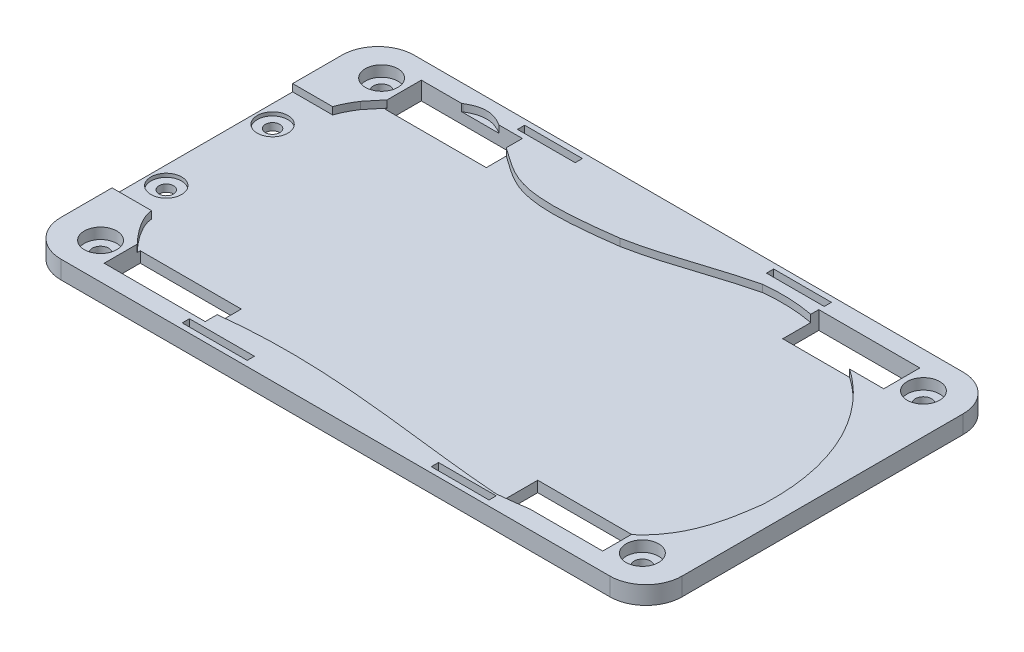
SolidWorks part; units mm, degrees
ref_plane "Front Plane" through (0, 0, 0) normal (0, 0, 1) x (1, 0, 0)
ref_plane "Top Plane" through (0, 0, 0) normal (0, 1, 0) x (1, 0, 0)
ref_plane "Right Plane" through (0, 0, 0) normal (1, 0, 0) x (0, 0, -1)
sketch "Sketch1" plane through (0, 0, 0) normal (0, 1, 0) x (1, 0, 0)
  line L1 (-78.1571, 35.933) -> (-78.1571, -14.1122)
  line L2 (78.9797, 0.0343) -> (-78.1571, 0.0343) construction
  line L3 (-77.1571, 35.7646) -> (-77.1571, -14.1122)
  line L4 (78.9797, -0.9657) -> (-78.1571, -0.9657)
  arc A1 (37.8695, -35.2975) -> (39.5975, -35.2134) centre (38.2635, -25.6055) ccw
  arc A2 (37.9263, -34.299) -> (39.4753, -34.2207) centre (38.2635, -25.6055) ccw
  spline S0 degree 1 poles (-77.1571, -14.1122) (-56.919, -31.9168) knots 0 0 1 1 construction
  spline S1 degree 1 poles (-56.919, -31.9168) (37.9263, -34.299) knots 0 0 1 1 construction
  spline S2 degree 1 poles (39.4753, -34.2207) (77.9849, 0.1477) knots 0 0 1 1 construction
  spline S3 degree 1 poles (77.9849, 0.1477) (25.0602, 52.8732) knots 0 0 1 1 construction
  spline S4 degree 1 poles (25.0602, 52.8732) (-5.6593, 44.1904) knots 0 0 1 1 construction
  spline S5 degree 1 poles (-5.6593, 44.1904) (-43.9853, 50.6886) knots 0 0 1 1 construction
  spline S6 degree 1 poles (-43.9853, 50.6886) (-59.7702, 54.7238) knots 0 0 1 1 construction
  spline S7 degree 1 poles (-59.7702, 54.7238) (-74.5158, 41.0521) knots 0 0 1 1 construction
  spline S8 degree 1 poles (-74.5158, 41.0521) (-77.1571, 35.7646) knots 0 0 1 1 construction
  spline S9 degree 3 poles (-77.1571, -14.1122) (-77.1565, -14.3701) (-77.1092, -14.8732) (-76.8359, -15.9559) (-76.1879, -17.5008) (-75.044, -19.4183) (-73.152, -22.0092) (-70.3495, -25.0822) (-66.8736, -28.0972) (-63.6864, -30.2141) (-61.0019, -31.4062) (-58.8274, -31.848) (-57.5718, -31.8794) (-56.919, -31.9168) knots 0.000484 0.000484 0.000484 0.000484 0.031521 0.062558 0.124632 0.186706 0.248781 0.372929 0.497077 0.621225 0.745373 0.869521 0.993669 0.993669 0.993669 0.993669
  spline S10 degree 3 poles (-56.919, -31.9168) (-56.6769, -31.8873) (-56.2021, -31.8274) (-55.1791, -31.687) (-53.8294, -31.4877) (-52.0759, -31.2184) (-49.5744, -30.8354) (-46.1465, -30.3372) (-41.5825, -29.7813) (-36.5976, -29.3261) (-29.4274, -28.913) (-19.5571, -28.8468) (-6.4839, -29.5875) (5.2448, -30.7865) (15.023, -31.9295) (22.521, -32.809) (30.1538, -33.642) (35.3408, -34.1075) (37.9263, -34.299) knots 0.000538 0.000538 0.000538 0.000538 0.016152 0.031766 0.062993 0.094221 0.125449 0.187904 0.250359 0.312815 0.37527 0.50018 0.625091 0.750001 0.812457 0.874912 0.937367 0.999822 0.999822 0.999822 0.999822
  spline S11 degree 3 poles (39.4753, -34.2207) (41.0079, -34.0574) (44.09, -33.7147) (50.0835, -32.8429) (57.0969, -31.1859) (64.2184, -27.8839) (69.7763, -23.1857) (73.0497, -18.2789) (74.9177, -14.0269) (75.9805, -10.7732) (76.7509, -7.5724) (77.1995, -5.064) (77.4798, -3.2279) (77.6607, -1.9649) (77.8261, -0.8108) (77.9301, -0.1834) (77.9849, 0.1477) knots -0.000309 -0.000309 -0.000309 -0.000309 0.063093 0.126495 0.253299 0.380104 0.506908 0.633712 0.697114 0.760516 0.823918 0.88732 0.919021 0.950722 0.982423 1.014124 1.014124 1.014124 1.014124
  spline S12 degree 3 poles (77.9849, 0.1477) (78.0286, 1.2633) (78.0637, 3.5224) (77.9426, 6.757) (77.6596, 9.9047) (77.0733, 13.9671) (75.9626, 18.7836) (73.4433, 25.9357) (69.0206, 33.8098) (62.0495, 41.4932) (53.7895, 47.3444) (44.6121, 51.2947) (34.9036, 53.2804) (28.3113, 53.2357) (25.0602, 52.8732) knots 0.000169 0.000169 0.000169 0.000169 0.031414 0.062658 0.093902 0.125147 0.187635 0.250124 0.375101 0.500079 0.625056 0.750034 0.875011 0.999988 0.999988 0.999988 0.999988
  spline S13 degree 3 poles (25.0602, 52.8732) (19.8954, 51.6294) (12.3224, 49.1317) (2.1607, 45.9713) (-3.0371, 44.6913) (-5.6593, 44.1904) knots 0.000659 0.000659 0.000659 0.000659 0.498067 0.746772 0.995476 0.995476 0.995476 0.995476
  spline S14 degree 3 poles (-5.6593, 44.1904) (-6.6879, 44.0461) (-8.7287, 43.7719) (-12.9633, 43.2668) (-18.1826, 42.7952) (-23.9015, 42.6322) (-28.8306, 42.9899) (-32.9666, 43.9514) (-35.9177, 45.2914) (-38.1959, 46.6779) (-39.9392, 47.8658) (-41.507, 48.9798) (-42.8638, 49.9292) (-43.6163, 50.4405) (-43.9853, 50.6886) knots -0.000196 -0.000196 -0.000196 -0.000196 0.062587 0.12537 0.250936 0.376501 0.502067 0.627632 0.753198 0.815981 0.878764 0.941546 0.972938 1.004329 1.004329 1.004329 1.004329
  spline S15 degree 3 poles (-43.9853, 50.6886) (-44.2445, 50.8673) (-44.7682, 51.2325) (-45.7507, 51.9331) (-46.8912, 52.7591) (-48.146, 53.6496) (-49.6971, 54.6811) (-51.4608, 55.6487) (-53.4077, 56.2593) (-55.2517, 56.3574) (-56.711, 56.0808) (-57.7948, 55.7138) (-58.5465, 55.3915) (-59.2299, 55.0428) (-59.5837, 54.8359) (-59.7702, 54.7238) knots -0.002497 -0.002497 -0.002497 -0.002497 0.029066 0.060629 0.123754 0.18688 0.250006 0.376257 0.502509 0.62876 0.755012 0.818137 0.881263 0.944389 1.007515 1.007515 1.007515 1.007515
  spline S16 degree 3 poles (-78.1571, -14.1122) (-78.1559, -14.7524) (-77.9173, -15.9777) (-77.0678, -17.9828) (-75.8538, -20.0098) (-73.8827, -22.6985) (-70.9901, -25.8584) (-67.4096, -28.9504) (-64.0991, -31.1349) (-61.2379, -32.3904) (-59.243, -32.7789) (-57.8421, -32.8756) (-57.2118, -32.9007) (-56.8882, -32.9203) knots 0.000409 0.000409 0.000409 0.000409 0.062843 0.125276 0.18771 0.250143 0.375011 0.499878 0.624745 0.749612 0.874479 0.936913 0.999346 0.999346 0.999346 0.999346
  spline S17 degree 3 poles (-56.8882, -32.9203) (-56.6427, -32.8908) (-56.1603, -32.8306) (-55.1309, -32.6904) (-53.7754, -32.491) (-52.0233, -32.2221) (-49.5292, -31.8398) (-46.1189, -31.3427) (-41.5829, -30.7872) (-36.6286, -30.3313) (-29.4997, -29.9158) (-19.6749, -29.8441) (-6.6369, -30.5782) (5.0856, -31.7749) (14.8757, -32.919) (22.3927, -33.8009) (30.0532, -34.6371) (35.2704, -35.1052) (37.8695, -35.2975) knots -0.001373 -0.001373 -0.001373 -0.001373 0.014273 0.029919 0.06121 0.092502 0.123794 0.186377 0.24896 0.311543 0.374127 0.499293 0.62446 0.749626 0.81221 0.874793 0.937376 0.99996 0.99996 0.99996 0.99996
  spline S18 degree 3 poles (39.5975, -35.2134) (41.1398, -35.049) (44.2356, -34.7045) (50.3018, -33.8209) (57.4502, -32.1301) (64.7991, -28.7164) (70.5782, -23.8111) (73.9656, -18.7006) (75.8832, -14.3057) (76.9672, -10.962) (77.7479, -7.6914) (78.1997, -5.145) (78.4804, -3.2966) (78.6613, -2.0308) (78.824, -0.9009) (78.9276, -0.2806) (78.9816, 0.0458) knots -0.000086 -0.000086 -0.000086 -0.000086 0.063428 0.126941 0.253967 0.380993 0.50802 0.635046 0.698559 0.762072 0.825585 0.889098 0.920855 0.952612 0.984368 1.016125 1.016125 1.016125 1.016125
  spline S19 degree 3 poles (78.9816, 0.0458) (79.0271, 1.1797) (79.0647, 3.4739) (78.9444, 6.7697) (78.6587, 9.9749) (78.0642, 14.1169) (76.9341, 19.0326) (74.3646, 26.3398) (69.8439, 34.3944) (62.712, 42.2543) (54.2626, 48.2351) (44.8799, 52.2671) (34.9529, 54.2886) (28.2109, 54.2351) (24.8869, 53.8601) knots -0.000407 -0.000407 -0.000407 -0.000407 0.03088 0.062166 0.093453 0.12474 0.187314 0.249888 0.375035 0.500183 0.62533 0.750478 0.875625 1.000773 1.000773 1.000773 1.000773
  spline S20 degree 3 poles (24.8869, 53.8601) (22.2839, 53.2349) (17.1223, 51.77) (6.9788, 48.4835) (-0.6206, 46.1711) (-5.8226, 45.1772) knots -0.001281 -0.001281 -0.001281 -0.001281 0.247714 0.49671 0.9947 0.9947 0.9947 0.9947
  spline S21 degree 3 poles (-5.8226, 45.1772) (-6.8463, 45.0337) (-8.8779, 44.761) (-13.0882, 44.2593) (-18.2643, 43.7927) (-23.9018, 43.6338) (-28.7026, 43.9859) (-32.6523, 44.9085) (-35.4477, 46.177) (-37.6484, 47.5152) (-39.3619, 48.6824) (-40.9248, 49.793) (-42.292, 50.7496) (-43.0505, 51.2651) (-43.4225, 51.5151) knots 0.000305 0.000305 0.000305 0.000305 0.063048 0.125791 0.251276 0.376761 0.502247 0.627732 0.753218 0.815961 0.878703 0.941446 0.972817 1.004189 1.004189 1.004189 1.004189
  spline S22 degree 3 poles (-43.4225, 51.5151) (-43.6786, 51.6918) (-44.1958, 52.0526) (-45.1684, 52.7462) (-46.308, 53.5714) (-47.577, 54.4721) (-49.1727, 55.5335) (-51.0441, 56.5648) (-53.2147, 57.2519) (-55.3195, 57.3652) (-56.9568, 57.0533) (-58.1477, 56.6506) (-58.9689, 56.2985) (-59.5708, 55.992) (-60.0059, 55.7483) (-60.1862, 55.6406) (-60.2803, 55.5839) knots -0.002294 -0.002294 -0.002294 -0.002294 0.029245 0.060783 0.12386 0.186936 0.250013 0.376167 0.50232 0.628473 0.754627 0.817704 0.88078 0.943857 0.975396 1.006934 1.006934 1.006934 1.006934
  spline S23 degree 3 poles (-60.2803, 55.5839) (-60.715, 55.3297) (-61.582, 54.801) (-63.2222, 53.7187) (-65.9105, 51.7373) (-69.2431, 48.741) (-72.0244, 45.6929) (-73.7392, 43.6279) (-74.6657, 42.4756) (-75.1049, 41.9202) (-75.3265, 41.639) knots 0.000427 0.000427 0.000427 0.000427 0.063268 0.126109 0.251792 0.503158 0.754524 0.880206 0.943048 1.005889 1.005889 1.005889 1.005889
  spline S24 degree 3 poles (-59.7702, 54.7238) (-60.1936, 54.4761) (-61.0386, 53.9612) (-62.6368, 52.9072) (-65.2587, 50.9763) (-68.5171, 48.0498) (-71.2443, 45.0657) (-73.1899, 42.7247) (-74.0698, 41.6179) (-74.5158, 41.0521) knots 0.000174 0.000174 0.000174 0.000174 0.062881 0.125589 0.251004 0.501833 0.752662 0.878077 1.003492 1.003492 1.003492 1.003492
  spline S25 degree 3 poles (-74.5158, 41.0521) (-75.0658, 40.2217) (-76.0765, 38.4779) (-76.8336, 36.6875) (-77.1571, 35.7646) knots 0.499549 0.499549 0.499549 0.499549 0.499766 0.499983 0.499983 0.499983 0.499983
  spline S26 degree 3 poles (-75.3265, 41.639) (-75.92, 40.746) (-77.0064, 38.8701) (-77.815, 36.9314) (-78.1571, 35.933) knots 0.499546 0.499546 0.499546 0.499546 0.49977 0.499995 0.499995 0.499995 0.499995
  point P0 (0.4631, 0.0343)
  dimension "D1" = 1
sketch "Sketch6" plane through (0, 0, 0) normal (0, 1, 0) x (1, 0, 0)
  line L0 (-78.1571, 35.933) -> (-78.1571, -14.1122) construction
  line L1 (73.9816, 59.5839) -> (-78.1571, 59.5839)
  line L2 (83.9816, 49.5839) -> (83.9816, -28.2975)
  line L3 (73.9816, -38.2975) -> (-78.1571, -38.2975)
  line L4 (-88.1571, 49.5839) -> (-88.1571, -28.2975)
  arc A0 (-78.1571, -38.2975) -> (-88.1571, -28.2975) centre (-78.1571, -28.2975) cw
  arc A1 (-88.1571, 49.5839) -> (-78.1571, 59.5839) centre (-78.1571, 49.5839) cw
  arc A2 (73.9816, 59.5839) -> (83.9816, 49.5839) centre (73.9816, 49.5839) cw
  arc A3 (83.9816, -28.2975) -> (73.9816, -38.2975) centre (73.9816, -28.2975) cw
  dimension "D5" = 10
  dimension "D1" = 5
  dimension "D2" = 10
  dimension "D3" = 3
  dimension "D4" = 4
extrude "Boss-Extrude2" add sketch "Sketch6" along normal blind 6.5
extrude "Cut-Extrude1" cut sketch "Sketch1" along normal blind 2.5 contours A2 S11 L4 L3 S9 S10 | S24 S25 L3 L4 S11 S12 S13 S14 S15 region at (0.1139, 0, 15.5782) region at (-2.2602, 0, -23.2786)
sketch "Sketch7" plane through (0, 0, 0) normal (0, -1, 0) x (1, 0, 0)
  line L1 (-76.2189, 14.1122) -> (-91.3452, 14.1122)
  line L2 (-76.2189, 14.1122) -> (-76.2189, -35.933)
  line L3 (-76.2189, -35.933) -> (-91.3452, -35.933)
  line L4 (-91.3452, 14.1122) -> (-91.3452, -35.933)
extrude "Cut-Extrude2" cut sketch "Sketch7" against normal up to surface (2.5 mm away) contours L2 L1 L4 L3 up to face at (-19.4492, 2.5, -12.7234)
sketch "Sketch8" plane through (0, 6.5, 0) normal (0, 1, 0) x (1, 0, 0)
  line L0 (83.9816, 10.6432) -> (-88.1571, 10.6432) construction
  line L1 (83.9816, -28.2975) -> (83.9816, 49.5839) construction
  line L2 (-88.1571, 49.5839) -> (-88.1571, -28.2975) construction
  line L3 (-2.0877, 59.5839) -> (-2.0877, -38.2975) construction
  line L4 (73.9816, 59.5839) -> (-78.1571, 59.5839) construction
  line L5 (-78.1571, -38.2975) -> (73.9816, -38.2975) construction
  line L7 (78.9816, 54.5839) -> (38.9816, 54.5839)
  line L8 (78.9816, 54.5839) -> (78.9816, 44.5839)
  line L9 (78.9816, 44.5839) -> (38.9816, 44.5839)
  line L10 (38.9816, 54.5839) -> (38.9816, 44.5839)
  line L22 (38.9816, 49.5839) -> (78.9816, 49.5839) construction
  line L23 (66.9816, 54.5839) -> (66.9816, 44.5839)
  circle A1 centre (72.9816, 49.5839) radius 3.5
  dimension "D6" = 7
  dimension "D1" = 10
  dimension "D2" = 40
  dimension "D3" = 5
  dimension "D4" = 5
  dimension "D5" = 6
  dimension "D7" = 6
sketch "Sketch9" plane through (0, 0, 0) normal (0, -1, 0) x (1, 0, 0)
  circle A0 centre (72.9816, -49.5839) radius 4.5
  dimension "D1" = 9
extrude "Cut-Extrude5" cut sketch "Sketch9" against normal blind 3.5
sketch "Sketch10" plane through (0, 3.5, 0) normal (0, -1, 0) x (1, 0, 0)
  circle A0 centre (72.9816, -49.5839) radius 2.25
  dimension "D1" = 4.5
extrude "Cut-Extrude6" cut sketch "Sketch10" against normal blind 21
extrude "Cut-Extrude8" cut sketch "Sketch8" against normal blind 42 contours L23 L7 L10 L9 region at (52.9816, 6.5, -49.5839)
extrude "Cut-Extrude9" cut sketch "Sketch8<3>" against normal blind 1 contours L7 L23 L9 L8 A1 region at (78.8254, 6.5, -49.5839)
sketch "Sketch8<3>" plane through (0, 6.5, 0) normal (0, 1, 0) x (1, 0, 0) same geometry as "Sketch8"
sketch "Sketch12" plane through (0, 6.5, 0) normal (0, 1, 0) x (1, 0, 0)
  line L0 (-88.1571, 10.6432) -> (83.9816, 10.6432) construction
  line L1 (-88.1571, 49.5839) -> (-88.1571, -28.2975) construction
  line L2 (83.9816, -28.2975) -> (83.9816, 49.5839) construction
  line L3 (-2.0877, 59.5839) -> (-2.0877, -36.8461) construction
  line L4 (73.9816, 59.5839) -> (-78.1571, 59.5839) construction
ref_plane "Plane1" through (0, 0, -10.6432) normal (0, 0, 1) x (1, 0, 0)
ref_plane "Plane2" through (-2.0877, 0, 0) normal (-1, 0, 0) x (0, 0, 1)
mirror "Mirror1" about plane through (0, 0, -10.6432) normal (0, 0, 1) of "Cut-Extrude5", "Cut-Extrude6", "Cut-Extrude8", "Cut-Extrude9"
mirror "Mirror2" about plane through (-2.0877, 0, 0) normal (-1, 0, 0) of "Mirror1", "Cut-Extrude9", "Cut-Extrude8", "Cut-Extrude6", "Cut-Extrude5"
sketch "Sketch13" plane through (0, 6.5, 0) normal (0, 1, 0) x (1, 0, 0)
  line L0 (-83.1571, 44.5839) -> (-43.1571, 44.5839) construction
  line L1 (58.9816, 39.5839) -> (-63.1571, 39.5839)
  line L2 (58.9816, 39.5839) -> (58.9816, -18.2975)
  line L3 (58.9816, -18.2975) -> (-63.1571, -18.2975)
  line L4 (-63.1571, 39.5839) -> (-63.1571, -18.2975)
  line L5 (58.9816, 39.5839) -> (-63.1571, -18.2975) construction
  line L6 (58.9816, -18.2975) -> (-63.1571, 39.5839) construction
  line L7 (-83.1571, -23.2975) -> (-43.1571, -23.2975) construction
  line L8 (83.9816, -28.2975) -> (83.9816, 49.5839) construction
  line L9 (-88.1571, 49.5839) -> (-88.1571, -28.2975) construction
  point P0 (-2.0877, 10.6432)
  dimension "D1" = 5
  dimension "D2" = 5
  dimension "D3" = 25
  dimension "D4" = 25
extrude "Cut-Extrude10" cut sketch "Sketch13" against normal blind 1
sketch "Sketch14" plane through (0, 5.5, 0) normal (0, 1, 0) x (1, 0, 0)
  line L0 (-63.1571, 10.6432) -> (58.9816, 10.6432) construction
  line L1 (-63.1571, 39.5839) -> (-63.1571, -18.2975) construction
  line L2 (58.9816, -18.2975) -> (58.9816, 39.5839) construction
  line L3 (-63.1571, -9.3568) -> (58.9816, -9.3568) construction
  line L4 (-63.1571, 10.6432) -> (58.9816, 10.6432) construction
  line L5 (-63.1571, 30.6432) -> (58.9816, 30.6432) construction
  circle A1 centre (-12.0877, 10.6432) radius 2.5
  circle A2 centre (-32.0877, 10.6432) radius 2.5
  circle A3 centre (-52.0877, 10.6432) radius 2.5
  circle A4 centre (-12.0877, 10.6432) radius 2.5
  circle A5 centre (-32.0877, 10.6432) radius 2.5
  circle A6 centre (7.9123, 10.6432) radius 2.5
  circle A7 centre (-12.0877, 10.6432) radius 2.5
  circle A8 centre (27.9123, 10.6432) radius 2.5
  circle A9 centre (7.9123, 10.6432) radius 2.5
  circle A10 centre (7.9123, 10.6432) radius 2.5
  circle A11 centre (27.9123, 10.6432) radius 2.5
  circle A12 centre (47.9123, 10.6432) radius 2.5
  circle A13 centre (-12.0877, -9.3568) radius 2.5
  circle A14 centre (-32.0877, -9.3568) radius 2.5
  circle A15 centre (-52.0877, -9.3568) radius 2.5
  circle A16 centre (-12.0877, -9.3568) radius 2.5
  circle A17 centre (-32.0877, -9.3568) radius 2.5
  circle A18 centre (7.9123, -9.3568) radius 2.5
  circle A19 centre (-12.0877, -9.3568) radius 2.5
  circle A20 centre (27.9123, -9.3568) radius 2.5
  circle A21 centre (7.9123, -9.3568) radius 2.5
  circle A22 centre (7.9123, -9.3568) radius 2.5
  circle A23 centre (27.9123, -9.3568) radius 2.5
  circle A24 centre (47.9123, -9.3568) radius 2.5
  circle A25 centre (-12.0877, 10.6432) radius 2.5
  circle A26 centre (-32.0877, 10.6432) radius 2.5
  circle A27 centre (-52.0877, 10.6432) radius 2.5
  circle A28 centre (-12.0877, 10.6432) radius 2.5
  circle A29 centre (-32.0877, 10.6432) radius 2.5
  circle A30 centre (7.9123, 10.6432) radius 2.5
  circle A31 centre (-12.0877, 10.6432) radius 2.5
  circle A32 centre (27.9123, 10.6432) radius 2.5
  circle A33 centre (7.9123, 10.6432) radius 2.5
  circle A34 centre (7.9123, 10.6432) radius 2.5
  circle A35 centre (27.9123, 10.6432) radius 2.5
  circle A36 centre (47.9123, 10.6432) radius 2.5
  circle A37 centre (-12.0877, 30.6432) radius 2.5
  circle A38 centre (-32.0877, 30.6432) radius 2.5
  circle A39 centre (-52.0877, 30.6432) radius 2.5
  circle A40 centre (-12.0877, 30.6432) radius 2.5
  circle A41 centre (-32.0877, 30.6432) radius 2.5
  circle A42 centre (7.9123, 30.6432) radius 2.5
  circle A43 centre (-12.0877, 30.6432) radius 2.5
  circle A44 centre (27.9123, 30.6432) radius 2.5
  circle A45 centre (7.9123, 30.6432) radius 2.5
  circle A46 centre (7.9123, 30.6432) radius 2.5
  circle A47 centre (27.9123, 30.6432) radius 2.5
  circle A48 centre (47.9123, 30.6432) radius 2.5
  point P8 (-2.0877, 10.6432)
  point P37 (-2.0877, -9.3568)
  point P64 (-2.0877, 10.6432)
  point P91 (-2.0877, 30.6432)
  dimension "D2" = 5
  dimension "D1" = 10
  dimension "D3" = 3
  dimension "D4" = 4
  dimension "D5" = 2
  dimension "D6" = 2
extrude "Cut-Extrude11" cut sketch "Sketch14" against normal blind 57 contours A39 | A42 | A44 | A48 | A12 | A6 | A1 | A2 | A3 | A24 | A20 | A18 | A13 | A14 | A15 | A38 | A37 | A8 region at (-12.0877, 5.5, -10.6432) region at (-32.0877, 5.5, -10.6432) region at (-52.0877, 5.5, -10.6432) region at (7.9123, 5.5, -10.6432) region at (47.9123, 5.5, -10.6432) region at (-12.0877, 5.5, 9.3568) region at (-32.0877, 5.5, 9.3568) region at (-52.0877, 5.5, 9.3568) region at (7.9123, 5.5, 9.3568) region at (27.9123, 5.5, 9.3568) region at (47.9123, 5.5, 9.3568) region at (-52.0877, 5.5, -30.6432) region at (7.9123, 5.5, -30.6432) region at (27.9123, 5.5, -30.6432) region at (47.9123, 5.5, -30.6432)
sketch "Sketch16" plane through (0, 0, 0) normal (0, -1, 0) x (1, 0, 0)
  line L0 (78.9816, -0.5458) -> (78.9816, -79.1994) construction
  line L1 (22.9816, -56.0839) -> (-37.6427, -56.0839) construction
  line L2 (73.9816, -59.5839) -> (-78.1571, -59.5839) construction
  line L3 (38.9816, -54.3238) -> (38.9816, 38.2975) construction
  line L4 (38.9816, -59.5839) -> (38.9816, -54.3238) construction
  line L5 (38.9816, -56.0839) -> (22.9816, -56.0839)
  line L6 (38.9816, -56.0839) -> (38.9816, -58.0839)
  line L7 (38.9816, -58.0839) -> (22.9816, -58.0839)
  line L8 (22.9816, -56.0839) -> (22.9816, -58.0839)
  line L9 (-78.1571, 38.2975) -> (73.9816, 38.2975) construction
  line L10 (22.9816, -56.0839) -> (22.9816, 38.2975) construction
  line L12 (38.9816, 36.7975) -> (22.9816, 36.7975)
  line L13 (38.9816, 36.7975) -> (38.9816, 34.7975)
  line L14 (38.9816, 34.7975) -> (22.9816, 34.7975)
  line L15 (22.9816, 36.7975) -> (22.9816, 34.7975)
  line L16 (22.9816, 34.7975) -> (-46.0184, 34.7975) construction
  line L17 (-30.0184, -56.0839) -> (-46.0184, -56.0839)
  line L18 (-30.0184, -56.0839) -> (-30.0184, -58.0839)
  line L19 (-30.0184, -58.0839) -> (-46.0184, -58.0839)
  line L20 (-46.0184, -56.0839) -> (-46.0184, -58.0839)
  line L22 (-28.0184, 34.7975) -> (-46.0184, 34.7975)
  line L23 (-28.0184, 34.7975) -> (-28.0184, 36.7975)
  line L24 (-28.0184, 36.7975) -> (-46.0184, 36.7975)
  line L25 (-46.0184, 34.7975) -> (-46.0184, 36.7975)
  dimension "D1" = 40
  dimension "D2" = 16
  dimension "D3" = 1.5
  dimension "D4" = 2
  dimension "D5" = 2
  dimension "D6" = 1.5
  dimension "D7" = 125
  dimension "D8" = 16
  dimension "D9" = 2
  dimension "D10" = 18
  dimension "D11" = 2
extrude "Cut-Extrude12" cut sketch "Sketch16" against normal blind 57
sketch "Sketch17" plane through (0, 5.5, 0) normal (0, 1, 0) x (1, 0, 0)
  line L1 (-99.5963, 69.0247) -> (98.4238, 69.0247)
  line L2 (-99.5963, 69.0247) -> (-99.5963, -53.2143)
  line L3 (-99.5963, -53.2143) -> (98.4238, -53.2143)
  line L4 (98.4238, 69.0247) -> (98.4238, -53.2143)
extrude "Cut-Extrude14" cut sketch "Sketch17" along normal blind 48.5
sketch "Sketch23" plane through (0, 2.5, 0) normal (0, -1, 0) x (1, 0, 0)
  line L0 (-88.1571, -10.9104) -> (-64.7808, -10.9104) construction
  line L1 (-88.1571, -35.933) -> (-88.1571, 14.1122) construction
  circle A0 centre (-83.1571, 4.0896) radius 2
  circle A1 centre (-83.1571, 4.0896) radius 4.25
  dimension "D1" = 4
  dimension "D4" = 8.5
  dimension "D2" = 15
  dimension "D3" = 5
extrude "Cut-Extrude15" cut sketch "Sketch23" against normal blind 48.5 contours A0
extrude "Cut-Extrude16" cut sketch "Sketch23<3>" against normal blind 1
sketch "Sketch23<3>" plane through (0, 2.5, 0) normal (0, -1, 0) x (1, 0, 0) same geometry as "Sketch23"
mirror "Mirror4" about plane through (0, 0, -10.6432) normal (0, 0, 1) of "Cut-Extrude16", "Cut-Extrude15"
sketch "Sketch24" plane through (0, 5.5, 0) normal (0, 1, 0) x (1, 0, 0)
  circle A0 centre (-77.1571, 49.5839) radius 3.25
  circle A1 centre (-77.1571, 49.5839) radius 2.25
  circle A2 centre (72.9816, 49.5839) radius 2.25
  circle A3 centre (72.9816, 49.5839) radius 3.25
  circle A4 centre (72.9816, -28.2975) radius 2.25
  circle A5 centre (-77.1571, -28.2975) radius 2.25
  circle A6 centre (-77.1571, -28.2975) radius 3.25
  circle A7 centre (72.9816, -28.2975) radius 3.25
  dimension "D1" = 6.5
  dimension "D2" = 6.5
  dimension "D3" = 6.5
  dimension "D4" = 6.5
extrude "Boss-Extrude3" add sketch "Sketch24" along normal blind 3
ref_plane "Plane3" through (0, 0, 0) normal (0, -1, 0) x (-1, 0, 0)
mirror "Mirror5" about plane through (0, 0, 0) normal (0, -1, 0) of "Boss-Extrude3", "Mirror4", "Cut-Extrude16", "Cut-Extrude15", "Cut-Extrude14", "Cut-Extrude12", "Cut-Extrude10", "Mirror2", "Mirror1", "Cut-Extrude9", "Cut-Extrude8", "Cut-Extrude6", "Cut-Extrude5", "Cut-Extrude2", "Cut-Extrude1", "Boss-Extrude2", "Cut-Extrude11"
sketch "Sketch25" plane through (0, 5.5, 0) normal (0, 1, 0) x (1, 0, 0)
  line L1 (-109.2871, 73.7066) -> (111.0455, 73.7066)
  line L2 (-109.2871, 73.7066) -> (-109.2871, -75.7235)
  line L3 (-109.2871, -75.7235) -> (111.0455, -75.7235)
  line L4 (111.0455, 73.7066) -> (111.0455, -75.7235)
extrude "Cut-Extrude18" cut sketch "Sketch25" against normal up to surface (5.5 mm away) and the other way blind 10 contours L2 L1 L4 L3 up to plane "Plane3"
ref_plane "Plane4" through (-77.0974, 0, 0) normal (-1, 0, 0) x (0, 0, 1)
ref_plane "Plane6" through (0, 0, -35.933) normal (0, 0, 1) x (1, 0, 0)
sketch "Sketch26" plane through (0, 0, 0) normal (0, 1, 0) x (1, 0, 0)
  line L1 (-104.6518, 69.0589) -> (106.0904, 69.0589)
  line L2 (-104.6518, 69.0589) -> (-104.6518, -52.1551)
  line L3 (-104.6518, -52.1551) -> (106.0904, -52.1551)
  line L4 (106.0904, 69.0589) -> (106.0904, -52.1551)
extrude "Cut-Extrude19" cut sketch "Sketch26" against normal blind 0.5
sketch "Sketch27" plane through (0, -2.5, 0) normal (0, 1, 0) x (1, 0, 0)
  line L1 (-59.9586, 37.3138) -> (59.6605, 37.3138)
  line L2 (-59.9586, 37.3138) -> (-59.9586, -15.8502)
  line L3 (-59.9586, -15.8502) -> (59.6605, -15.8502)
  line L4 (59.6605, 37.3138) -> (59.6605, -15.8502)
extrude "Boss-Extrude4" add sketch "Sketch27" against normal up to surface (3 mm away) up to face at (72.9816, -5.5, 25.0475)
